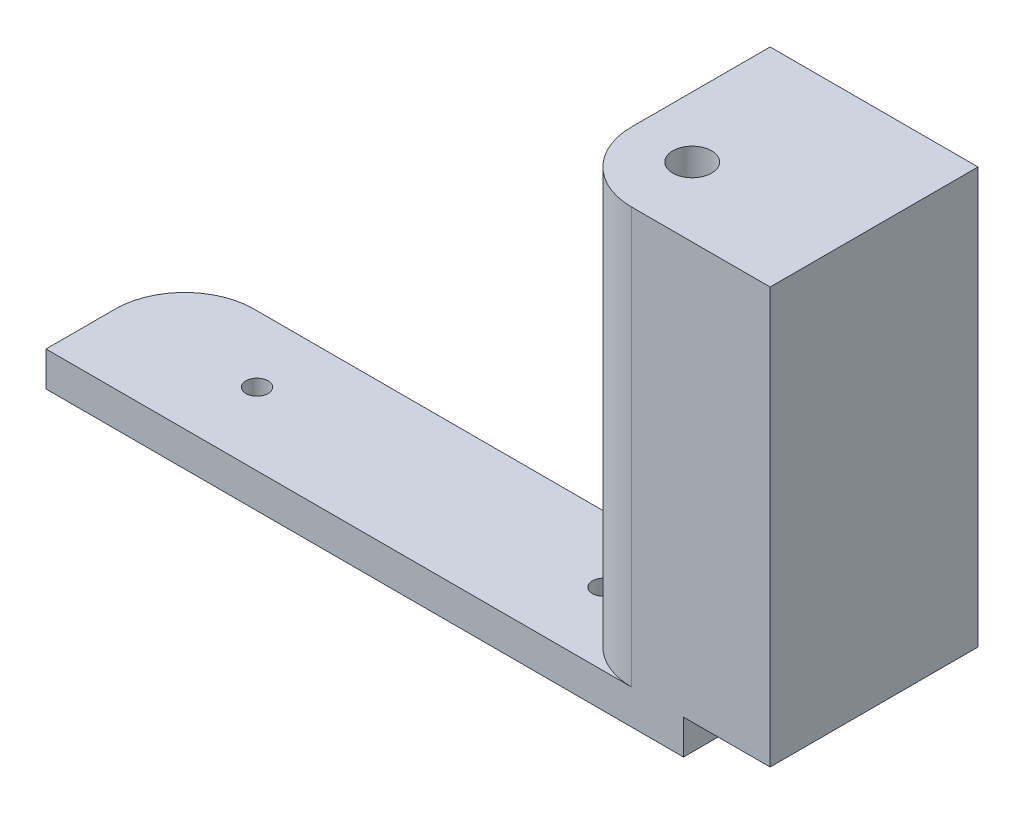
SolidWorks part; units mm, degrees
ref_plane "Front Plane" through (0, 0, 0) normal (0, 0, 1) x (1, 0, 0)
ref_plane "Top Plane" through (0, 0, 0) normal (0, 1, 0) x (1, 0, 0)
ref_plane "Right Plane" through (0, 0, 0) normal (1, 0, 0) x (0, 0, -1)
sketch "Sketch1" plane through (0, 0, 0) normal (0, 1, 0) x (1, 0, 0)
  line L1 (-46, -10) -> (46, -10)
  line L2 (-46, -10) -> (-46, 10)
  line L3 (-46, 10) -> (46, 10)
  line L4 (46, -10) -> (46, 10)
  line L5 (-46, -10) -> (46, 10) construction
  line L6 (-46, 10) -> (46, -10) construction
  point P0 (0, 0)
  dimension "D1" = 92
  dimension "D2" = 20
extrude "Boss-Extrude1" add sketch "Sketch1" along normal blind 5
fillet "Fillet1" radius 10 2 edges at (46, 2.5, -10) (-46, 2.5, -10)
sketch "Sketch2" plane through (0, 5, 0) normal (0, 1, 0) x (1, 0, 0)
  line L0 (-46, 0) -> (-46, -10) construction
  line L1 (-46, -10) -> (46, -10) construction
  circle A0 centre (-26, 0.45) radius 1.6
  circle A2 centre (24, 0.45) radius 1.6
  dimension "D1" = 3.2
  dimension "D2" = 3.2
  dimension "D3" = 20
  dimension "D4" = 50
  dimension "D5" = 10.45
extrude "Cut-Extrude1" cut sketch "Sketch2" against normal blind 5
sketch "Sketch3" plane through (0, 5, 0) normal (0, 1, 0) x (1, 0, 0)
  line L7 (28.5, -10) -> (28.5, 20)
  line L8 (-46, -10) -> (46, -10) construction
  line L9 (28.5, 20) -> (58.5, 20)
  line L10 (58.5, 20) -> (58.5, -10)
  line L11 (58.5, -10) -> (28.5, -10)
  circle A1 centre (24, 0.45) radius 1.6 construction
  dimension "D1" = 4.5
  dimension "D2" = 30
  dimension "D3" = 30
extrude "Boss-Extrude2" add sketch "Sketch3" along normal blind 60
sketch "Sketch4" plane through (0, 65, 0) normal (0, 1, 0) x (1, 0, 0)
  circle A0 centre (37.25, 0) radius 2.8
  dimension "D1" = 5.6
extrude "Cut-Extrude2" cut sketch "Sketch4" against normal blind 45
fillet "Fillet5" radius 10 1 edges at (28.5, 35, 10)
